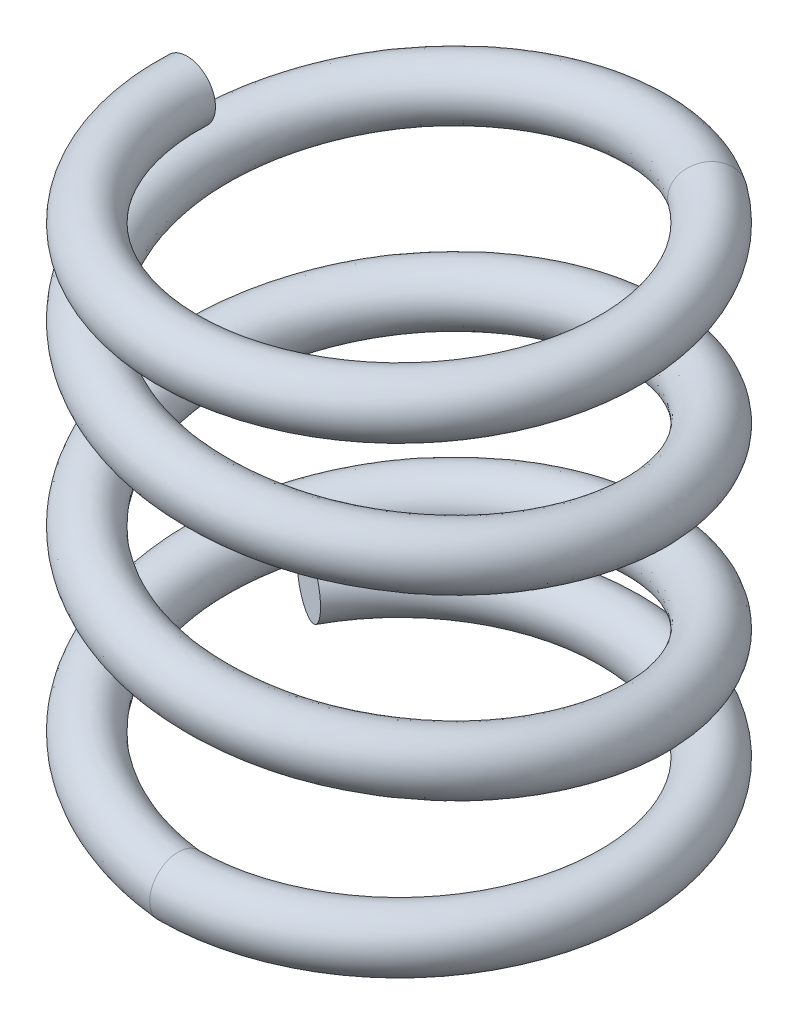
SolidWorks part; units mm, degrees
ref_plane "Front Plane" through (0, 0, 0) normal (0, 0, 1) x (1, 0, 0)
ref_plane "Top Plane" through (0, 0, 0) normal (0, 1, 0) x (1, 0, 0)
ref_plane "Right Plane" through (0, 0, 0) normal (1, 0, 0) x (0, 0, -1)
sketch "Sketch1" plane through (0, 0, 0) normal (0, 1, 0) x (1, 0, 0)
  circle A0 centre (0, 0) radius 3.1
  dimension "D1" = 6.2
curve "Helix/Spiral1" pitch 2.5 height 6.5 radius 3.1 left hand yes centre (0, 0, 0) axis (0, 1, 0) start towards (0, 0, 1)
sketch "Sketch3" plane through (0, 0, 0) normal (1, 0, 0) x (0, 0, -1)
  circle A0 centre (-3.1, 0) radius 0.4
  spline S0 degree 3 poles (-3.1, 0) (-3.1, 0.0525) (-2.9338, 0.1587) (-2.2248, 0.317) (-1.1672, 0.4756) (0.0732, 0.6341) (1.3021, 0.7927) (2.3271, 0.9512) (2.9874, 1.1098) (3.1798, 1.2683) (2.8739, 1.4268) (2.1178, 1.5854) (1.0299, 1.7439) (-0.2193, 1.9024) (-1.4342, 2.061) (-2.4244, 2.2195) (-3.0348, 2.378) (-3.1697, 2.5366) (-2.808, 2.6951) (-2.0064, 2.8537) (-0.8904, 3.0122) (0.3651, 3.1707) (1.5633, 3.3293) (2.5166, 3.4878) (3.0757, 3.6463) (3.1529, 3.8049) (2.7361, 3.9634) (1.8907, 4.122) (0.749, 4.2805) (-0.51, 4.439) (-1.6891, 4.5976) (-2.6036, 4.7561) (-3.1101, 4.9146) (-3.1294, 5.0732) (-2.6585, 5.2317) (-1.771, 5.3902) (-0.606, 5.5488) (0.6539, 5.7073) (1.8113, 5.8659) (2.685, 6.0244) (3.1378, 6.183) (3.1001, 6.3413) (2.7484, 6.4475) (2.508, 6.5) knots 0 0 0 0 0.02439 0.04878 0.073171 0.097561 0.121951 0.146341 0.170732 0.195122 0.219512 0.243902 0.268293 0.292683 0.317073 0.341463 0.365854 0.390244 0.414634 0.439024 0.463415 0.487805 0.512195 0.536585 0.560976 0.585366 0.609756 0.634146 0.658537 0.682927 0.707317 0.731707 0.756098 0.780488 0.804878 0.829268 0.853659 0.878049 0.902439 0.926829 0.95122 0.97561 1 1 1 1 construction
  dimension "D1" = 0.8
sweep "Sweep2" add profiles "Sketch3" path "Helix/Spiral1"
sketch "Sketch7" plane through (0, 0, 0) normal (0, 1, 0) x (1, 0, 0)
  line L0 (0, -3.5) -> (0, -2.7) construction
  arc A0 (0, -3.1) -> (-2.7314, 1.4662) centre (0, 0) ccw
  dimension "D1" = 6.2
sketch "Sketch8" plane through (0, 0, 0) normal (1, 0, 0) x (0, 0, -1)
  line L0 (3.1, 0) -> (-3.1, 0) construction
  circle A0 centre (-3.1, 0) radius 0.4
sweep "Sweep3" add profiles "Sketch8" path "Sketch7"
sketch "Sketch10" plane through (0, 0, 0) normal (0.809, 0, 0.5878) x (0.5878, 0, -0.809)
  circle A0 centre (3.1, 6.5) radius 0.4
  circle A1 centre (3.1, 6.5) radius 0.4 construction
  point P2 (3.1, 6.5)
ref_plane "Plane1" through (0, 6.5, 0) normal (0, 1, 0) x (1, 0, 0)
sketch "Sketch12" plane through (0, 6.5, 0) normal (0, 1, 0) x (1, 0, 0)
  arc A0 (1.8221, 2.508) -> (-3.0969, 0.1388) centre (0, 0) cw
sweep "Sweep4" add profiles "Sketch10" path "Sketch12"
sketch "Sketch4" plane through (0, 0, 0) normal (1, 0, 0) x (0, 0, -1)
  line L0 (0.3739, 6.9) -> (0.1389, 6.9) construction
  line L1 (-3.1, -0.4) -> (-4.5425, -0.4) construction
  circle A3 centre (-3.1, 0) radius 0.4 construction
  ellipse E0 centre (0.1388, 6.5) end of major axis (0.1388, 6.1) minor radius 0.0179 construction
sketch "Sketch5" plane through (0, 0, 0) normal (0, 1, 0) x (1, 0, 0)
  circle A0 centre (0, 0) radius 3.5 construction
  circle A1 centre (0, 0) radius 2.7 construction
  circle A2 centre (0, 0) radius 3.1 construction
  dimension "D1" = 7
  dimension "D2" = 6.2
  dimension "D3" = 5.4
